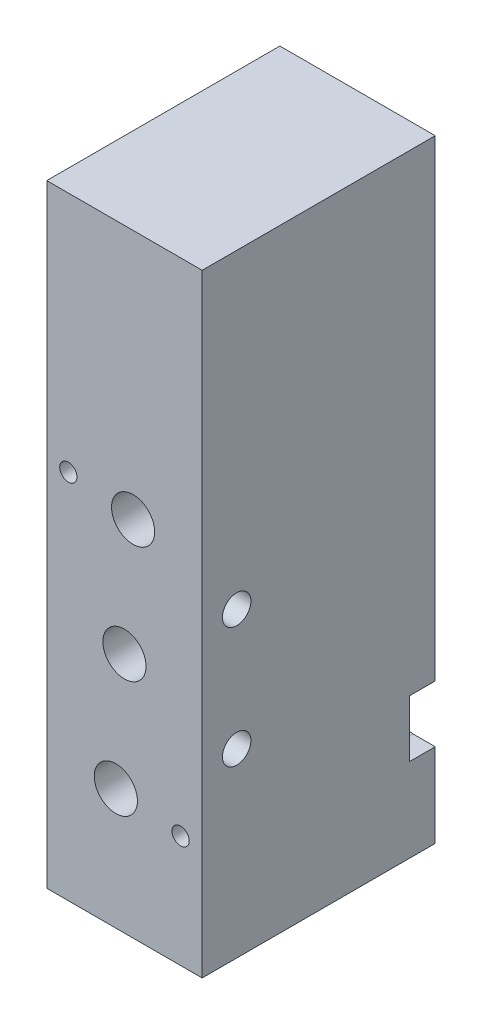
SolidWorks part; units mm, degrees
ref_plane "Plan de face" through (0, 0, 0) normal (0, 0, 1) x (1, 0, 0)
ref_plane "Plan de dessus" through (0, 0, 0) normal (0, 1, 0) x (1, 0, 0)
ref_plane "Plan de droite" through (0, 0, 0) normal (1, 0, 0) x (0, 0, -1)
sketch "Esquisse1" plane through (0, 0, 0) normal (1, 0, 0) x (0, 0, -1)
  line L0 (48.6356, 136.3934) -> (247.1534, 136.3934) construction
  line L1 (120.9287, 62.2621) -> (147.9287, 62.2621)
  line L2 (120.9287, 62.2621) -> (120.9287, 133.2621)
  line L3 (120.9287, 133.2621) -> (147.9287, 133.2621)
  line L4 (147.9287, 133.2621) -> (147.9287, 62.2621)
  dimension "D1" = 27
  dimension "D2" = 71
extrude "Boss.-Extru.1" add sketch "Esquisse1" along normal blind 18
sketch "Esquisse2" plane through (0, 0, 0) normal (-1, 0, 0) x (0, 0, 1)
  line L0 (-120.9287, 62.2621) -> (-147.9287, 62.2621) construction
  line L1 (-120.9287, 62.2621) -> (-120.9287, 133.2621) construction
  circle A0 centre (-124.9287, 97.2621) radius 1.65
  circle A1 centre (-124.9287, 83.2621) radius 1.65
  dimension "D1" = 3.3
  dimension "D2" = 3.3
  dimension "D3" = 14
  dimension "D4" = 21
  dimension "D5" = 4
extrude "Enlèv. mat.-Extru.1" cut sketch "Esquisse2" against normal through all
sketch "Esquisse5" plane through (0, 0, -147.9287) normal (0, 0, -1) x (-1, 0, 0)
  line L0 (65.581, 62.4584) -> (92.581, 62.4584) construction
  line L1 (-18, 133.2621) -> (0, 133.2621) construction
  line L2 (95.255, 123.6955) -> (-25.8368, 123.6955) construction
  circle A0 centre (-9, 123.6955) radius 2
  point P6 (-9, 133.2621)
  dimension "D2" = 4
  dimension "D1" = 27
extrude "Boss.-Extru.2" add sketch "Esquisse5" along normal blind 2.5
sketch "Esquisse6" plane through (0, 0, -147.9287) normal (0, 0, -1) x (-1, 0, 0)
  line L0 (-9, 133.2621) -> (-9, 62.2621) construction
  line L1 (-18, 133.2621) -> (0, 133.2621) construction
  line L2 (-18, 62.2621) -> (0, 62.2621) construction
  circle A0 centre (-10.5, 82.2621) radius 2.5
  circle A1 centre (-7.5, 98.2621) radius 2.5
  dimension "D3" = 5
  dimension "D4" = 5
  dimension "D1" = 1.5
  dimension "D2" = 1.5
  dimension "D5" = 20
  dimension "D6" = 16
extrude "Enlèv. mat.-Extru.2" cut sketch "Esquisse6" against normal blind 4
sketch "Esquisse7" plane through (0, 0, -147.9287) normal (0, 0, -1) x (-1, 0, 0)
  line L0 (-2.5, 108.5621) -> (0, 108.5621)
  line L1 (0, 62.2621) -> (0, 133.2621) construction
  line L2 (-2.5302, 101.9622) -> (0, 101.9622)
  line L3 (-18, 62.2621) -> (0, 62.2621) construction
  line L4 (-15.5, 78.5621) -> (-18, 78.5621)
  line L5 (-18, 62.2621) -> (-18, 133.2621) construction
  line L6 (-15.4518, 71.9624) -> (-18, 71.9624)
  line L7 (-15.5, 75.2621) -> (-18, 75.2621) construction
  line L8 (-2.5, 105.2621) -> (0, 105.2621) construction
  circle A0 centre (-2.5, 105.2621) radius 1
  arc A1 (-2.5, 108.5621) -> (-2.5302, 101.9622) centre (-2.5, 105.2621) ccw
  circle A2 centre (-15.5, 75.2621) radius 1
  arc A3 (-15.5, 78.5621) -> (-15.4518, 71.9624) centre (-15.5, 75.2621) cw
  line M9 (0, 62.2621) -> (0, 133.2621)
  line M11 (-18, 133.2621) -> (-18, 62.2621)
  dimension "D1" = 3.3
  dimension "D2" = 2
  dimension "D4" = 2
  dimension "D5" = 3.3
  dimension "D3" = 43
  dimension "D6" = 13
  dimension "D7" = 13
extrude "Enlèv. mat.-Extru.3" cut sketch "Esquisse7" against normal blind 3 contours A0 | L0 A1 L2 A0 M9 | A3 L4 L6 A2 M11 | A2 region at (1.25, 108.4742, -147.9287) region at (12.2879, 75.2855, -147.9287) region at (2.5, 105.2621, -147.9287) region at (15.5, 75.2621, -147.9287)
extrude "Enlèv. mat.-Extru.4" cut sketch "Esquisse7<3>" against normal through all contours A0 | A2 region at (2.5, 105.2621, -147.9287) region at (15.5, 75.2621, -147.9287)
sketch "Esquisse7<3>" plane through (0, 0, -147.9287) normal (0, 0, -1) x (-1, 0, 0) same geometry as "Esquisse7"
sketch "Esquisse8" plane through (0, 0, -120.9287) normal (0, 0, 1) x (1, 0, 0)
  line L0 (0.0619, 62.7432) -> (18.0619, 62.7432) construction
  line L1 (9, 62.2621) -> (9, 133.2621) construction
  line L2 (18, 62.2621) -> (0, 62.2621) construction
  line L3 (18, 133.2621) -> (0, 133.2621) construction
  line L4 (10, 104.2621) -> (9, 104.2621) construction
  line L5 (8, 76.2621) -> (9, 76.2621) construction
  circle A0 centre (8, 76.2621) radius 2.5
  circle A1 centre (9, 90.2621) radius 2.5
  circle A2 centre (10, 104.2621) radius 2.5
  dimension "D6" = 5
  dimension "D7" = 5
  dimension "D8" = 5
  dimension "D1" = 18
  dimension "D2" = 2
  dimension "D3" = 14
  dimension "D4" = 28
  dimension "D5" = 28
extrude "Enlèv. mat.-Extru.5" cut sketch "Esquisse8" against normal blind 4
sketch "Esquisse9" plane through (0, 133.2621, 0) normal (0, 1, 0) x (1, 0, 0)
  line L0 (9, 147.9287) -> (9, 120.9287) construction
  line L1 (18, 147.9287) -> (0, 147.9287) construction
  line L2 (18, 120.9287) -> (0, 120.9287) construction
  line L3 (0, 134.4287) -> (18, 134.4287) construction
  line L4 (0, 147.9287) -> (0, 120.9287) construction
  line L5 (18, 147.9287) -> (18, 120.9287) construction
